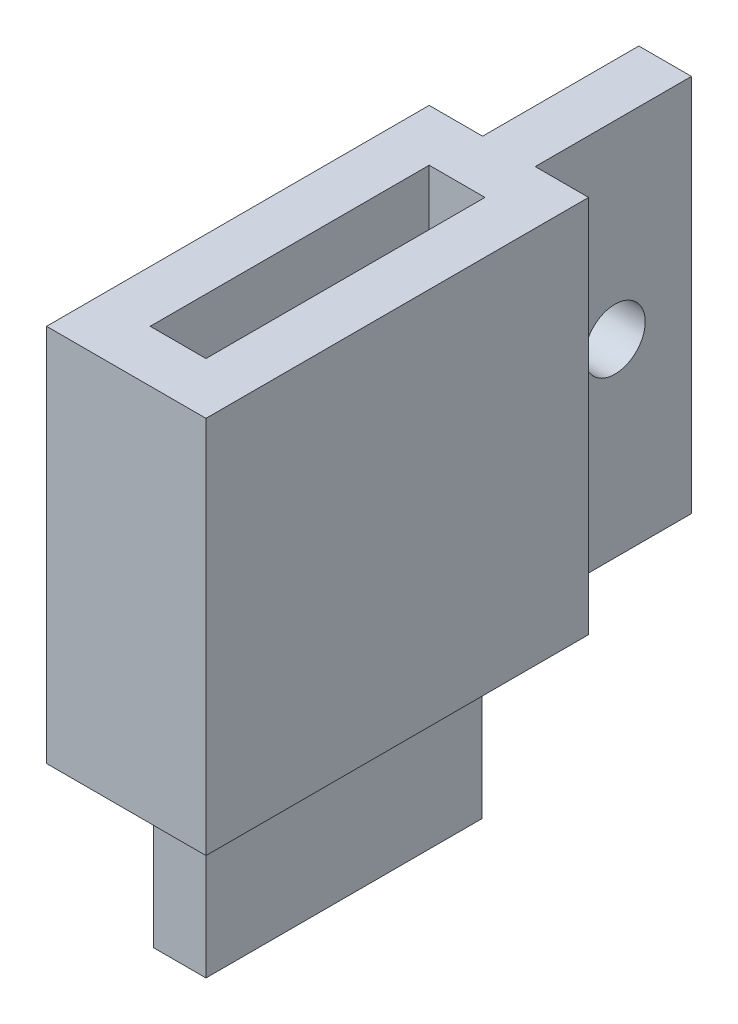
SolidWorks part; units mm, degrees
ref_plane "Front Plane" through (0, 0, 0) normal (1, 0, 0) x (0, 1, 0)
ref_plane "Top Plane" through (0, 0, 0) normal (0, 0, 1) x (0, 1, 0)
ref_plane "Right Plane" through (0, 0, 0) normal (0, 1, 0) x (-1, 0, 0)
sketch "Sketch1" plane through (0, 0, 0) normal (1, 0, 0) x (0, 1, 0)
  line L1 (0, 0) -> (23.75, 0)
  line L2 (0, 0) -> (0, 24)
  line L3 (0, 24) -> (23.75, 24)
  line L4 (23.75, 0) -> (23.75, 24)
  dimension "D1" = 23.75
  dimension "D2" = 24
extrude "Boss-Extrude1" add sketch "Sketch1" against normal blind 10
sketch "Sketch2" plane through (0, 0, 0) normal (0, -1, 0) x (1, 0, 0)
  line L1 (-10, 0) -> (-6.65, 0)
  line L2 (-10, 0) -> (-10, -9.8)
  line L3 (-10, -9.8) -> (-6.65, -9.8)
  line L4 (-6.65, 0) -> (-6.65, -9.8)
  line L5 (0, 0) -> (-3.35, 0)
  line L6 (0, 0) -> (0, -9.8)
  line L7 (0, -9.8) -> (-3.35, -9.8)
  line L8 (-3.35, 0) -> (-3.35, -9.8)
  line L9 (-6.65, -9.8) -> (-3.35, -9.8)
  line L10 (-6.65, -9.8) -> (-6.65, 0)
  line L11 (-6.65, 0) -> (-3.35, 0)
  line L12 (-3.35, -9.8) -> (-3.35, 0)
  line M12 (-10, 0) -> (0, 0)
  dimension "D1" = 9.8
  dimension "D2" = 3.35
  dimension "D3" = 3.35
extrude "Boss-Extrude2" add sketch "Sketch2" against normal through all contours L4 L9 L8 M12 region at (-5, 0, -4.9)
sketch "Sketch3" plane through (0, 0, 0) normal (0, -1, 0) x (1, 0, 0)
  line L0 (-3.35, 20.65) -> (-3.35, 3.35)
  line L1 (0, 24) -> (-10, 24)
  line L2 (0, 24) -> (0, 0)
  line L3 (0, 0) -> (-10, 0)
  line L4 (-10, 24) -> (-10, 0)
  line L5 (-3.35, 3.35) -> (-6.65, 3.35)
  line L6 (-6.65, 20.65) -> (-6.65, 3.35)
  line L7 (-3.35, 20.65) -> (-6.65, 20.65)
  dimension "D1" = 3.35
extrude "Boss-Extrude3" add sketch "Sketch3" along normal blind 10 contours L0 L7 L6 L5 region at (-5, 0, 12)
sketch "Sketch4" plane through (-6.65, 0, 0) normal (-1, 0, 0) x (0, -1, 0)
  line L0 (0, 0) -> (-23.75, 0) construction
  line L1 (-11.875, 0) -> (-23.75, 0)
  line L2 (-11.875, 0) -> (-11.875, -5)
  line L3 (-11.875, -5) -> (-23.75, -5)
  line L4 (-23.75, 0) -> (-23.75, -5)
  circle A0 centre (-11.875, -5) radius 1.9
  dimension "D2" = 3.8
  dimension "D1" = 5
extrude "Cut-Extrude1" cut sketch "Sketch4" against normal up to next contours A0
sketch "Sketch5" plane through (0, 23.75, 0) normal (0, 1, 0) x (-1, 0, 0)
  line L0 (3.25, 20.75) -> (3.25, 3.25)
  line L1 (0, 24) -> (10, 24)
  line L2 (0, 24) -> (0, 0)
  line L3 (0, 0) -> (10, 0)
  line L4 (10, 24) -> (10, 0)
  line L5 (3.25, 3.25) -> (6.75, 3.25)
  line L6 (6.75, 20.75) -> (6.75, 3.25)
  line L7 (3.25, 20.75) -> (6.75, 20.75)
  dimension "D1" = 3.25
extrude "Cut-Extrude2" cut sketch "Sketch5" against normal blind 10 contours L7 L0 L5 L6 region at (-5, 23.75, 12)
equation "\"whitekey_cutout_length\"= 101.5"
equation "\"key_mount_recess_length\"=50"
equation "\"key_mount_recess_height\"=12.5"
equation "\"key_mount_recess_depth\"=1.5"
equation "\"wall_thickness\"=10"
equation "\"guide_brace_height\"=20"
equation "\"guide_brace_thickness\"=2"
equation "\"dowel_recess_depth\"=10"
equation "\"dowel_recess_offset\"=3.25"
equation "\"base_mount_height\"=40"
equation "\"base_rear_length\"=80"
equation "\"base_front_length\"=111.5"
equation "\"screw_hole_wall_offset\"=7.25"
equation "\"screw_hole_edge_inset\"=\"dowel_recess_depth\"/2"
equation "\"screw_hole_diameter\"=3.8"
equation "\"screw_head_hole_diameter\"=6.7"
equation "\"screw_nut_hole_side_len\"=3.5"
equation "\"screw_shaft_diameter\"=3.5"
equation "\"switch_board_width\"=30"
equation "\"switch_board_wall_offset\"=11.5"
equation "\"heatset_insert_hole_diameter\"=4.8"
equation "\"heatset_insert_hole_depth\"=3.8"
equation "\"D1@Boss-Extrude1\"=\"wall_thickness\""
equation "\"D2@Sketch2\"=\"dowel_recess_offset\"+0.1"
equation "\"D3@Sketch2\"=\"dowel_recess_offset\"+0.1"
equation "\"D1@Boss-Extrude3\"=\"dowel_recess_depth\""
equation "\"D1@Sketch3\"=\"dowel_recess_offset\"+0.1"
equation "\"D1@Sketch2\"=\"dowel_recess_depth\"-0.2"
equation "\"D1@Sketch4\"=\"screw_hole_edge_inset\""
equation "\"D2@Sketch4\"=\"screw_hole_diameter\""
equation "\"D1@Sketch5\"=\"dowel_recess_offset\""
equation "\"D1@Cut-Extrude2\"=\"dowel_recess_depth\""
equation "\"screw_nut_recess_offset\"=0.35"
equation "\"screw_head_and_nut_recess_depth\"=2.5"
equation "\"front_rear_panel_width\"=23.75"
equation "\"rod_length_adj\"=0.5"
equation "\"rod_insert_length\"=2.8"
equation "\"D1@Sketch1\"=\"front_rear_panel_width\""
equation "\"switch_board_thickness\"=1.6"
equation "\"front_panel_height\"=24"
equation "\"rod_diameter\"=5"
equation "\"rod_head_diameter\"=8"
equation "\"switch_black_key_mount_height\"=8"
equation "\"switch_white_key_mount_height\"=3"
equation "\"D2@Sketch1\"=\"front_panel_height\""
